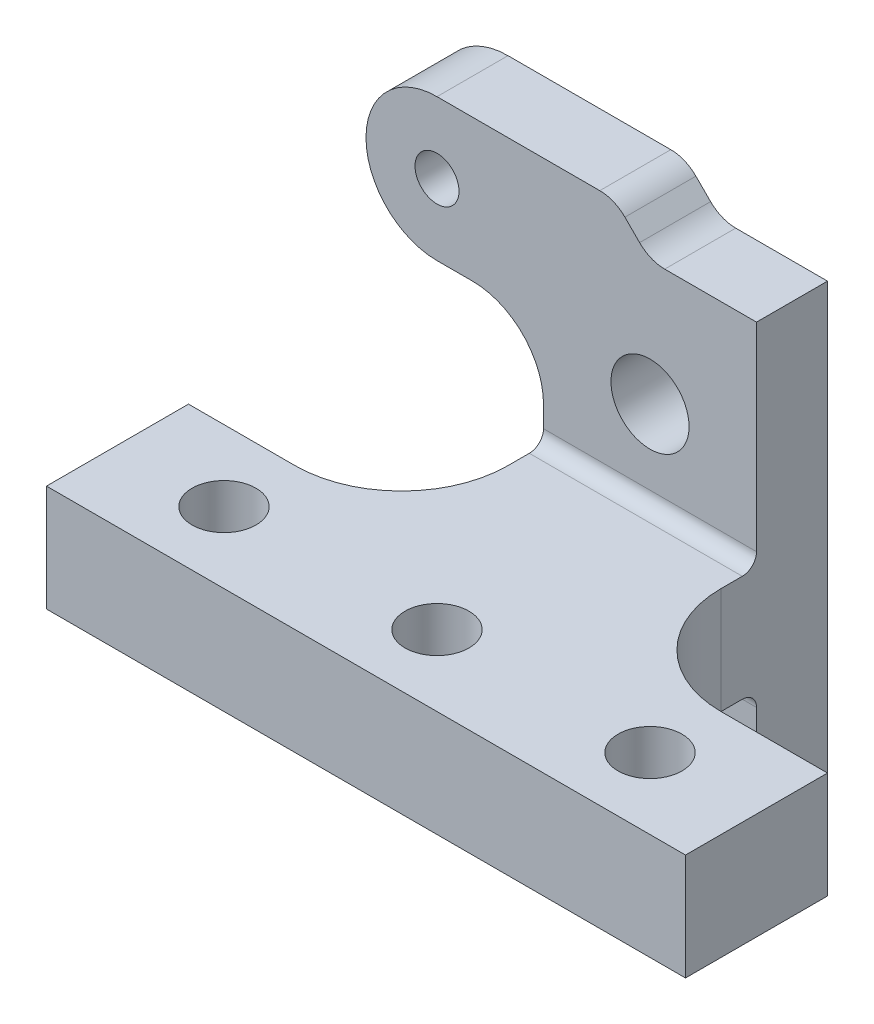
SolidWorks part; units mm, degrees
material "ABS"
ref_plane "前视基准面" through (0, 0, 0) normal (0, 0, 1) x (1, 0, 0)
ref_plane "上视基准面" through (0, 0, 0) normal (0, 1, 0) x (1, 0, 0)
ref_plane "右视基准面" through (0, 0, 0) normal (1, 0, 0) x (0, 0, -1)
sketch "草图1" plane through (0, 0, 0) normal (0, 0, 1) x (1, 0, 0)
  line L0 (0, 0) -> (0, 20) construction
  line L1 (-15, -37.5) -> (15, -37.5)
  line L2 (-15, -37.5) -> (-15, 37.5)
  line L3 (-15, 37.5) -> (15, 37.5)
  line L4 (15, -37.5) -> (15, 37.5)
  line L5 (-15, -37.5) -> (15, 37.5) construction
  line L6 (-15, 37.5) -> (15, -37.5) construction
  line L7 (0, 0) -> (0, -20) construction
  circle A0 centre (0, 20) radius 5.5
  circle A1 centre (0, -20) radius 5.5
  point P0 (0, 0)
  dimension "D3" = 11
  dimension "D4" = 11
  dimension "D1" = 30
  dimension "D2" = 75
extrude "凸台-拉伸1" add sketch "草图1" along normal blind 10
sketch "草图2" plane through (0, 0, 10) normal (0, 0, 1) x (1, 0, 0)
  line L0 (15, -37.5) -> (15, 37.5) construction
  line L1 (-15, 7.5) -> (15, 7.5)
  line L2 (-15, 7.5) -> (-15, -7.5)
  line L3 (-15, -7.5) -> (15, -7.5)
  line L4 (15, 7.5) -> (15, -7.5)
  line L5 (-15, 7.5) -> (15, -7.5) construction
  line L6 (-15, -7.5) -> (15, 7.5) construction
  point P0 (0, 0)
  dimension "D1" = 15
extrude "凸台-拉伸2" add sketch "草图2" along normal blind 40
fillet "圆角1" radius 2 2 edges at (0, 7.5, 10) (0, -7.5, 10)
sketch "草图3" plane through (0, -7.5, 0) normal (0, -1, 0) x (-1, 0, 0)
  line L0 (0, -10) -> (0, -40) construction
  line L1 (-15, -10) -> (15, -10) construction
  circle A0 centre (0, -40) radius 4.5
extrude "切除-拉伸1" cut sketch "草图3" against normal up to vertex (15 mm away) up to point (15, 7.5, 50)
sketch "草图5" plane through (15, 0, 0) normal (1, 0, 0) x (0, 0, -1)
  line L0 (-50, 7.5) -> (-12, 7.5) construction
  line L1 (-50, -7.5) -> (-30, -7.5)
  line L2 (-50, -7.5) -> (-50, 7.5)
  line L3 (-50, 7.5) -> (-30, 7.5)
  line L4 (-30, -7.5) -> (-30, 7.5)
  line L5 (-40, 7.5) -> (-40, -7.5) construction
  line L6 (-50, 0) -> (-30, 0) construction
  point P64 (-40, 0)
extrude "凸台-拉伸3" add sketch "草图5" along normal blind 30
sketch "草图6" plane through (0, -7.5, 0) normal (0, -1, 0) x (-1, 0, 0)
  line L0 (0, -40) -> (-30, -40) construction
  circle A0 centre (-30, -40) radius 4.5
extrude "切除-拉伸2" cut sketch "草图6" against normal blind 30
fillet "圆角2" radius 15 1 edges at (15, 0, 30)
sketch "草图7" plane through (-15, 0, 0) normal (-1, 0, 0) x (0, 0, 1)
  line L0 (50, -7.5) -> (12, -7.5) construction
  line L1 (50, 7.5) -> (30, 7.5)
  line L2 (50, 7.5) -> (50, -7.5)
  line L3 (50, -7.5) -> (30, -7.5)
  line L4 (30, 7.5) -> (30, -7.5)
  line L5 (40, -7.5) -> (40, 7.5) construction
  line L6 (50, 0) -> (30, 0) construction
  point P88 (40, 0)
extrude "凸台-拉伸4" add sketch "草图7" along normal blind 30
fillet "圆角3" radius 15 1 edges at (-15, 0, 30)
sketch "草图8" plane through (0, -7.5, 0) normal (0, -1, 0) x (-1, 0, 0)
  line L0 (0, -40) -> (30, -40) construction
  circle A0 centre (30, -40) radius 4.5
extrude "切除-拉伸3" cut sketch "草图8" against normal blind 30
sketch "草图9" plane through (0, 0, 10) normal (0, 0, 1) x (1, 0, 0)
  line L0 (-30, 42.5) -> (-5, 42.5)
  line L2 (15, 37.5) -> (-15, 37.5) construction
  line L3 (-30, 22.5) -> (-15, 22.5)
  line L4 (-15, 37.5) -> (-15, 9.5) construction
  line L5 (0, 37.5) -> (-15, 22.5)
  line L7 (-5, 42.5) -> (0, 37.5)
  arc A0 (-30, 42.5) -> (-30, 22.5) centre (-30, 32.5) ccw
extrude "凸台-拉伸5" add sketch "草图9" against normal blind 10
fillet "圆角4" radius 5 2 edges at (-5, 42.5, 5) (0, 37.5, 5)
fillet "圆角5" radius 10 1 edges at (-15, 22.5, 5)
sketch "草图10" plane through (0, 0, 10) normal (0, 0, 1) x (1, 0, 0)
  circle A0 centre (-30, 32.5) radius 3.1
extrude "切除-拉伸4" cut sketch "草图10" against normal blind 10
